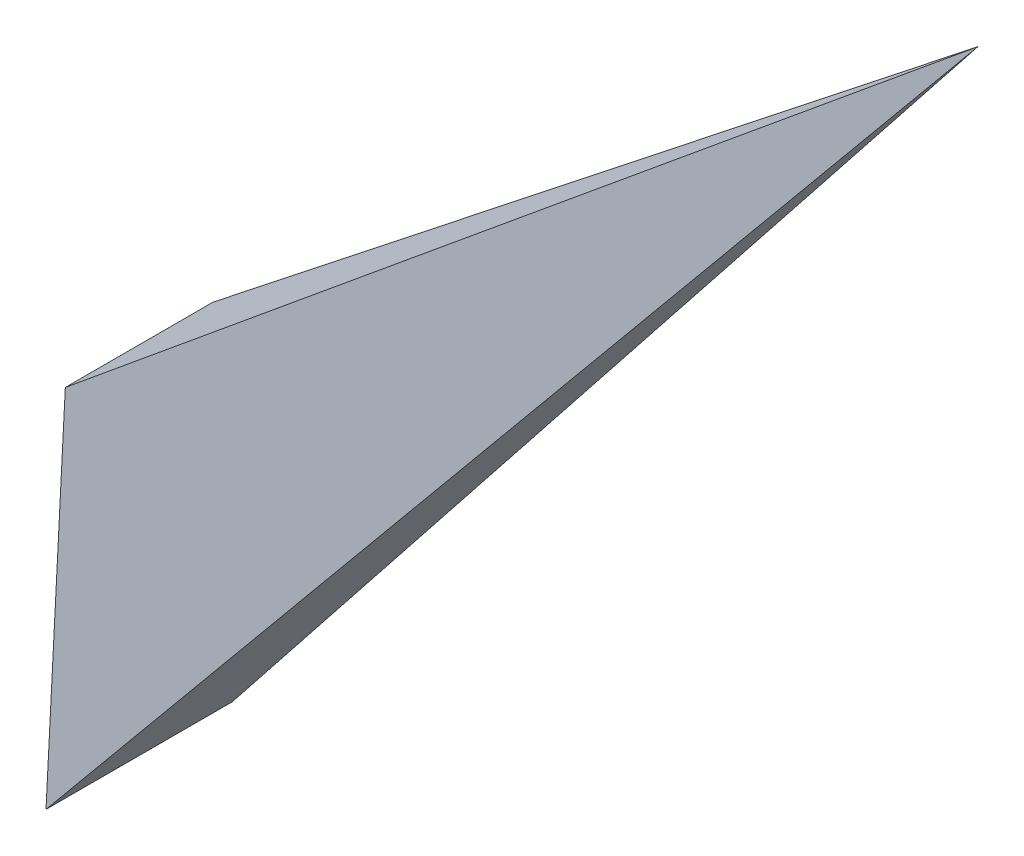
SolidWorks part; units mm, degrees
material "Custom Plastic"
ref_plane "Front Plane" through (0, 0, 0) normal (1, 0, 0) x (0, 1, 0)
ref_plane "Top Plane" through (0, 0, 0) normal (0, 0, 1) x (0, 1, 0)
ref_plane "Right Plane" through (0, 0, 0) normal (0, 1, 0) x (-1, 0, 0)
sketch "Sketch1" plane through (0, 0, 0) normal (0, 0, 1) x (0, 1, 0)
  line L0 (0, 0) -> (1219.2, 989.6853)
  line L1 (1219.2, 989.6853) -> (2438.4, 0)
  line L2 (2438.4, 0) -> (1473.632, 1194.2828)
  line L3 (1473.632, 1194.2828) -> (964.768, 1194.2828)
  line L4 (964.768, 1194.2828) -> (0, 0)
  line L5 (0, 0) -> (1091.984, 1091.984) construction
  line L6 (2438.4, 0) -> (1346.416, 1091.984) construction
  line L7 (964.768, 1194.2828) -> (1219.2, 989.6853) construction
  line L8 (1219.2, 989.6853) -> (1473.632, 1194.2828) construction
  line L9 (0, 0) -> (2438.4, 0) construction
  point P6 (1219.2, 0)
  point P10 (1091.984, 1091.984)
  point P12 (1346.416, 1091.984)
  point P18 (1219.2, 1194.2828)
  dimension "D1" = 90
  dimension "D2" = 12
  dimension "D4" = 2438.4
extrude "Boss-Extrude1" add sketch "Sketch1" along normal blind 508 and the other way blind 508
sketch "Sketch2" plane through (-1193.1555, 968.5436, 0) normal (0.7764, -0.6302, 0) x (0.6302, 0.7764, 0)
  line L0 (1893.1713, 0) -> (-138.8287, 142.0913)
  line L1 (1893.1713, -508) -> (1893.1713, 508) construction
  line L2 (322.8448, -508) -> (322.8448, 508) construction
  line L5 (322.8448, 0) -> (1893.1713, 0) construction
  line L6 (-138.8287, 142.0913) -> (-138.8287, 508)
  line L7 (-138.8287, 508) -> (1893.1713, 508)
  line L9 (-138.8287, -508) -> (1893.1713, -508)
  line L10 (-138.8287, -142.0913) -> (-138.8287, -508)
  line L11 (1893.1713, 0) -> (-138.8287, -142.0913)
  line L12 (1893.1713, 0) -> (1893.1713, 508)
  line L13 (1893.1713, 0) -> (1893.1713, -508)
  dimension "D1" = 4
  dimension "D2" = 2032
extrude "Cut-Extrude2" cut sketch "Sketch2" against normal through all and the other way through all contours L12 L7 L6 L0 | L13 L9 L10 L11
sketch "Sketch5" plane through (0, 0, 0) normal (0, 0, 1) x (0, 1, 0)
  line L0 (2438.4, 0) -> (965.7134, 1195.453)
  line L1 (965.7134, 1195.453) -> (0, 0)
  line L2 (0, 0) -> (2438.4, 0)
  line L5 (2438.4, 0) -> (1219.2, 989.6853) construction
  line L6 (0, 0) -> (964.768, 1194.2828) construction
extrude "Cut-Extrude7" cut sketch "Sketch5" against normal through all and the other way through all
